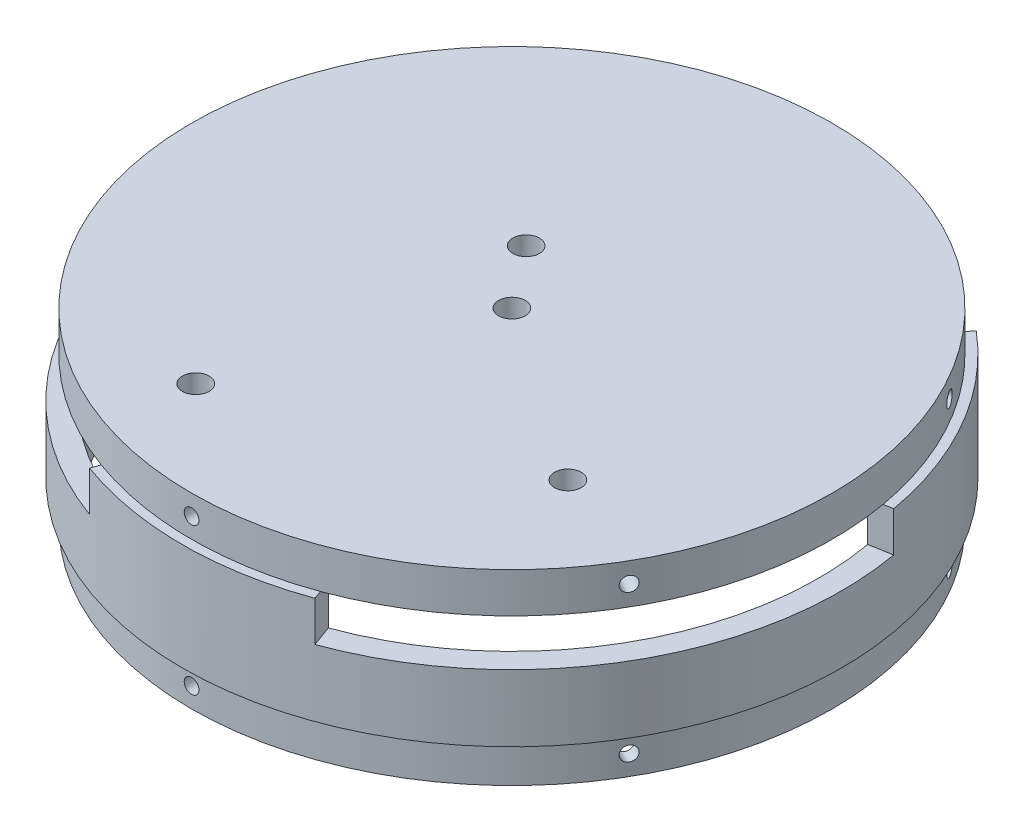
SolidWorks part; units mm, degrees
ref_plane "Front Plane" through (0, 0, 0) normal (0, 0, 1) x (1, 0, 0)
ref_plane "Top Plane" through (0, 0, 0) normal (0, 1, 0) x (1, 0, 0)
ref_plane "Right Plane" through (0, 0, 0) normal (1, 0, 0) x (0, 0, -1)
sketch "Sketch1" plane through (0, 0, 0) normal (0, 1, 0) x (1, 0, 0)
  line L0 (0, 0) -> (-50.3682, 60.0265)
  line L1 (0, 0) -> (50.3682, 60.0265)
  line L2 (0, 0) -> (0, 72.1431) construction
  circle A0 centre (0, 0) radius 78.359
  circle A1 centre (0, 0) radius 73.025
  circle A2 centre (0, 0) radius 76.1746
  dimension "D1" = 156.718
  dimension "D2" = 146.05
  dimension "D3" = 152.3492
  dimension "D4" = 80
extrude "Boss-Extrude1" add sketch "Sketch1" along normal blind 25.4 contours L2 A2 L1 A0 | L2 A1 L1 A2 | L2 A2 L1 A1 | L2 A0 L1 A2 | A2 L2 A1 L0 | A0 L2 A2 L0 | A2 L2 A0 L0 | A1 L2 A2 L0 region at (-31.7206, 0, 68.0251) region at (-47.1858, 0, -57.7895) region at (-33.0764, 0, 70.9325) region at (-48.8794, 0, -59.85)
ref_plane "Plane1" through (0, 12.7, 0) normal (0, 1, 0) x (1, 0, 0)
extrude "Boss-Extrude2" add sketch "Sketch1<3>" along normal blind 9.525 from surface contours A2 L2 A1 L0 | L2 A2 L1 A1 | L2 A1 L1 A2 | A1 L2 A2 L0 region at (-31.7206, 0, 68.0251) region at (-47.1858, 0, -57.7895) starting at face at (0, 25.4, 73.025)
sketch "Sketch1<3>" plane through (0, 0, 0) normal (0, 1, 0) x (1, 0, 0) same geometry as "Sketch1"
extrude "Boss-Extrude3" add sketch "Sketch1<4>" against normal blind 9.525 contours A2 L2 A1 L0 | A1 L2 A2 L0 | L2 A1 L1 A2 | L2 A2 L1 A1 region at (-31.7206, 0, 68.0251) region at (-47.1858, 0, -57.7895)
sketch "Sketch1<4>" plane through (0, 0, 0) normal (0, 1, 0) x (1, 0, 0) same geometry as "Sketch1"
ref_plane "Plane2" through (0, 0, -76.1746) normal (0, 0, -1) x (-1, 0, 0)
ref_plane "Plane5" through (0, 25.4, 0) normal (0, 1, 0) x (1, 0, 0)
ref_axis "Axis1" through (0, 0, 0) along (0, 1, 0)
sketch "Sketch3" plane through (0, 0, -76.1746) normal (0, 0, -1) x (-1, 0, 0)
  line L0 (76.1746, 0) -> (-76.1746, 0) construction
  line L1 (-76.1746, -9.525) -> (76.1746, -9.525) construction
  line L2 (76.1746, 25.4) -> (-76.1746, 25.4) construction
  line L3 (76.1746, 34.925) -> (-76.1746, 34.925) construction
  line L4 (76.1746, 0) -> (-76.1746, 0)
  line L5 (-76.1746, -9.525) -> (76.1746, -9.525)
  line L6 (76.1746, 25.4) -> (-76.1746, 25.4)
  line L7 (76.1746, 34.925) -> (-76.1746, 34.925)
  line L8 (0, 34.925) -> (0, 25.4)
  line L9 (0, 0) -> (0, -9.525)
  circle A0 centre (0, 30.1625) radius 1.75
  circle A1 centre (0, -4.7625) radius 1.75
  point P12 (0, 30.1625)
  point P13 (0, -4.7625)
  point P14 (-77.5445, 179.1871)
  dimension "D1" = 3.5
extrude "Cut-Extrude2" cut sketch "Sketch3" against normal blind 9.525 contours L8 A0 | L8 A0 | L9 A1 | L9 A1 region at (-0.7427, 30.1625, -76.1746) region at (0.7427, 30.1625, -76.1746) region at (-0.7427, -4.7625, -76.1746) region at (0.7427, -4.7625, -76.1746)
extrude "Cut-Extrude3" cut sketch "Sketch1<7>" against normal blind 9.525 from surface contours L2 A1 L1 A2 | A1 L2 A2 L0 | A2 L2 A0 L0 | L2 A2 L1 A0 region at (-47.1858, 0, -57.7895) region at (-48.8794, 0, -59.85) starting at plane "Plane5"
sketch "Sketch1<7>" plane through (0, 0, 0) normal (0, 1, 0) x (1, 0, 0) same geometry as "Sketch1"
pattern_circular "CirPattern2" count 3 over 360 about axis through (0, 0, 0) along (0, 1, 0) of "Cut-Extrude3"
ref_plane "Plane3" through (0, 34.925, 0) normal (0, 1, 0) x (1, 0, 0)
sketch "Sketch4" plane through (0, 34.925, 0) normal (0, 1, 0) x (1, 0, 0)
  circle A0 centre (0, 0) radius 73.025
  dimension "D1" = 146.05
extrude "Boss-Extrude4" add sketch "Sketch4" against normal blind 9.525
pattern_circular "CirPattern3" count 6 over 360 about axis through (0, 0, 0) along (0, 1, 0) of "Cut-Extrude2"
sketch "Sketch5" plane through (0, 34.925, 0) normal (0, 1, 0) x (1, 0, 0)
  line L0 (-15.0069, -36.2322) -> (-26.8004, -73.6334) construction
  line L1 (-15.0069, -36.2322) -> (-22.0157, -53.1519) construction
  circle A0 centre (0, 0) radius 3.175
  circle A1 centre (-22.0157, -53.1519) radius 3.175
  circle A2 centre (0, 0) radius 57.531 construction
  circle A3 centre (23.8745, -31.1125) radius 57.531 construction
  circle A4 centre (-11.1485, 14.5297) radius 3.175
  circle A5 centre (-15.0069, -36.2322) radius 57.531 construction
  circle A6 centre (42.0318, -28.7224) radius 3.175
  point P17 (2.9559, -22.4482)
  dimension "D1" = 6.35
  dimension "D3" = 6.35
  dimension "D2" = 57.531
  dimension "D5" = 5
extrude "Cut-Extrude4" cut sketch "Sketch5" against normal through all
equation "\"AB_Coupler_OD_Length\"= 1in"
equation "\"AB_Coupling_Section_Length\"= 0.375in"
equation "\"AB_Coupler_Length\"= \"AB_Coupler_OD_Length\" + \"AB_Coupling_Section_Length\" * 2"
equation "\"D1@Boss-Extrude2\"=\"AB_Coupling_Section_Length\""
equation "\"D1@Boss-Extrude3\"=\"AB_Coupling_Section_Length\""
equation "\"D1@Boss-Extrude1\" = \"AB_Coupler_OD_Length\""
equation "\"Cutout_Angle\" = 80"
equation "\"AB_Coupler_Num_Screws\"= 6"
equation "\"Num_Cutouts\" = 3"
equation "\"D4@Sketch1\"=\"Cutout_Angle\""
equation "\"D1@CirPattern2\"=\"Num_Cutouts\""
equation "\"D1@CirPattern3\"=\"AB_Coupler_Num_Screws\""
equation "\"AB_Coupler_OD\"= 6.17in"
equation "\"AB_Coupler_ID\"= 5.75in"
equation "\"AB_Coupler_Surface_Diameter\"= 5.998in"
equation "\"D3@Sketch1\"=\"AB_Coupler_Surface_Diameter\""
equation "\"D2@Sketch1\"=\"AB_Coupler_ID\""
equation "\"D1@Sketch1\"=\"AB_Coupler_OD\""
equation "\"AB_Coupling_Screw_Diameter\"= 0.1065in"
equation "\"Aft_Section_Length\"= 40in"
equation "\"Aft_Lower_Length\"= 20in"
equation "\"Aft_Upper_Length\"= \"Aft_Section_Length\" - \"Aft_Lower_Length\" - \"AB_Coupler_OD_Length\""
equation "\"Mid_Coupler_Length\" = 13in"
equation "\"Lead_Screw_Dist\" = 2.25in"
equation "\"Lead_Screw_Diam\" = (27/64)*1in"
equation "\"Lead_Screw_Length\" = (\"Mid_Coupler_Length\" + 2*0.375in + 2*0.5in)"
equation "\"Bodytube_OD\" = 6.17in"
equation "\"Paddle_Pin_Offset\" = .25in"
equation "\"Bodytube_ID\" = 5.998in"
equation "\"Paddle_Pin_Radius\" = 2.55in"
equation "\"D1@Sketch4\"=\"AB_Coupler_ID\""
equation "\"D2@Sketch5\"=2.265"
